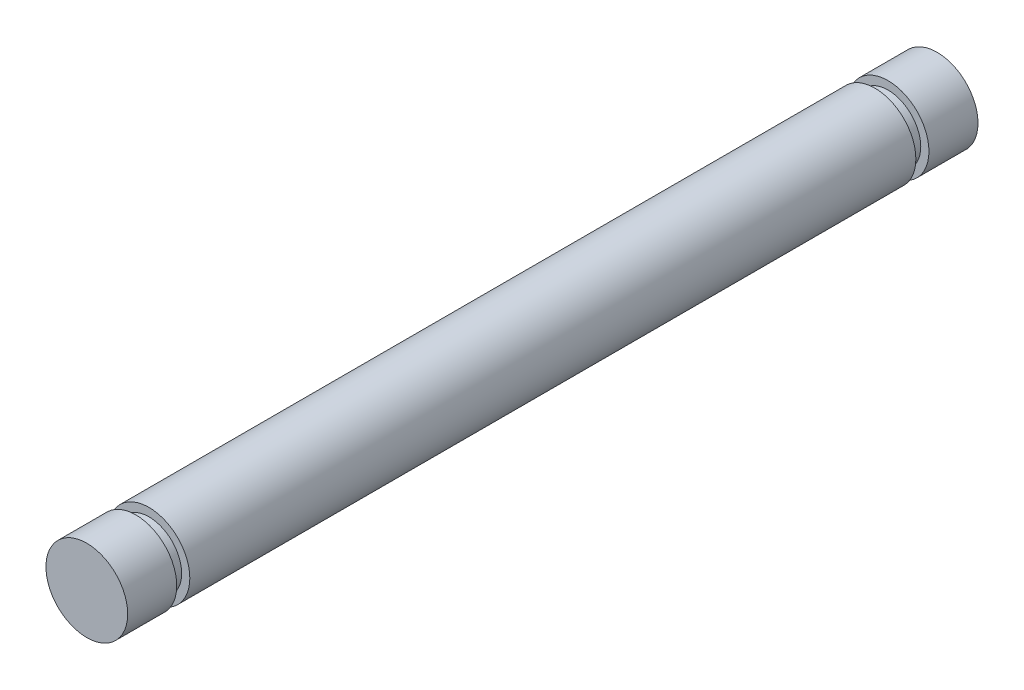
SolidWorks part; units mm, degrees
ref_plane "Front Plane" through (0, 0, 0) normal (0, 0, 1) x (1, 0, 0)
ref_plane "Top Plane" through (0, 0, 0) normal (0, 1, 0) x (1, 0, 0)
ref_plane "Right Plane" through (0, 0, 0) normal (1, 0, 0) x (0, 0, -1)
sketch "Sketch1" plane through (0, 0, 0) normal (1, 0, 0) x (0, 0, -1)
  line L0 (55, 0) -> (-55, 0) construction
  line L1 (-26, 0) -> (26, 0)
  line L2 (-26, 0) -> (-26, 2.5)
  line L3 (-26, 2.5) -> (-23, 2.5)
  line L4 (26, 0) -> (26, 2.5)
  line L5 (0, -11.3439) -> (0, 19.3783) construction
  line L6 (0, 55) -> (0, -55) construction
  line L7 (-22.2, 2.5) -> (-22.2, 2)
  line L8 (-22.2, 2) -> (-23, 2)
  line L9 (-23, 2) -> (-23, 2.5)
  line L10 (-22.2, 2.5) -> (22.2, 2.5)
  line L11 (22.2, 2.5) -> (22.2, 2)
  line L12 (22.2, 2) -> (23, 2)
  line L13 (23, 2) -> (23, 2.5)
  line L14 (23, 2.5) -> (26, 2.5)
  dimension "D1" = 52
  dimension "D2" = 2.5
  dimension "D3" = 3.8
  dimension "D4" = 0.5
  dimension "D5" = 0.8
revolve "Revolve1" add sketch "Sketch1" angle 360 about L1
